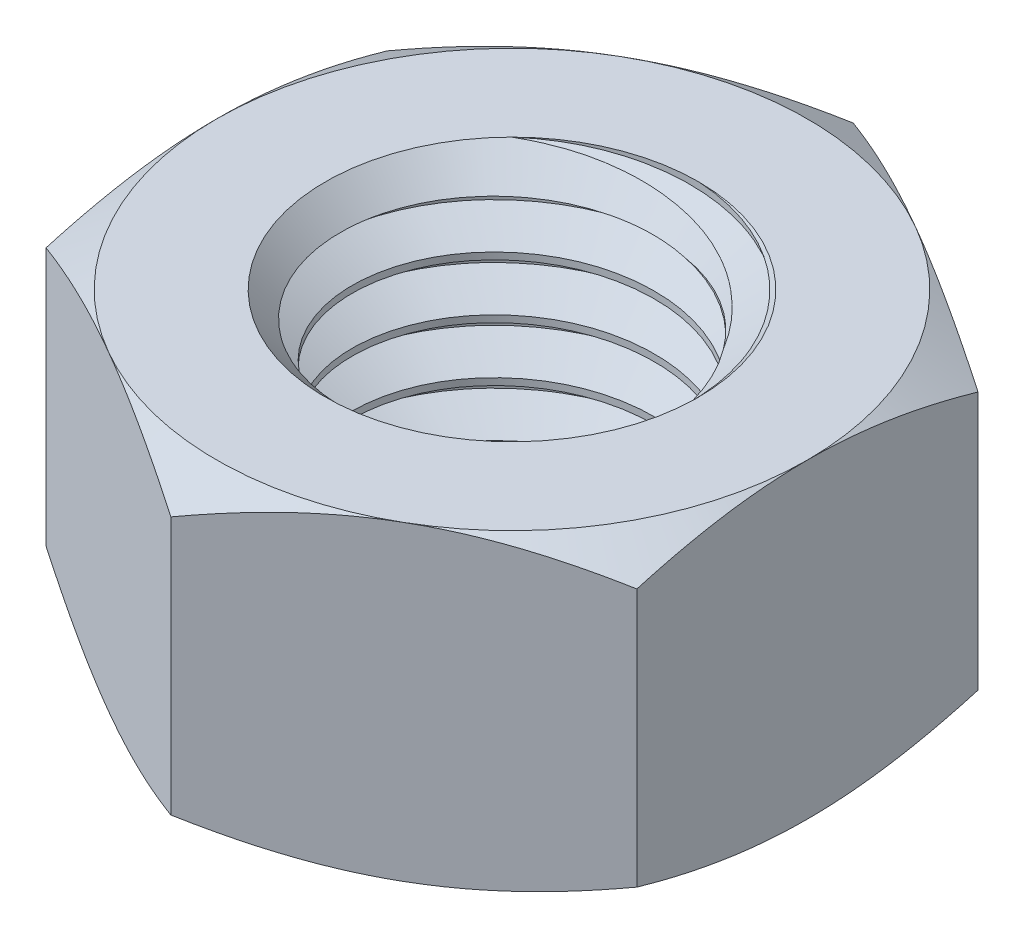
SolidWorks part; units mm, degrees
ref_plane "Front Plane" through (0, 0, 0) normal (0, 0, 1) x (1, 0, 0)
ref_plane "Top Plane" through (0, 0, 0) normal (0, 1, 0) x (1, 0, 0)
ref_plane "Right Plane" through (0, 0, 0) normal (1, 0, 0) x (0, 0, -1)
sketch "Sketch1" plane through (0, 0, 0) normal (0, 1, 0) x (1, 0, 0)
  line L0 (0, -6) -> (0, -4.25) construction
  line L1 (-9.5, 5.4848) -> (-9.5, -5.4848)
  line L2 (-9.5, -5.4848) -> (0, -10.9697)
  line L3 (0, -10.9697) -> (9.5, -5.4848)
  line L4 (9.5, -5.4848) -> (9.5, 5.4848)
  line L5 (9.5, 5.4848) -> (0, 10.9697)
  line L6 (0, 10.9697) -> (-9.5, 5.4848)
  line L7 (0, 6) -> (0, 4.25) construction
  circle A0 centre (0, 0) radius 9.5 construction
  circle A1 centre (0, 0) radius 6
  point P14 (0, 5.125)
  point P15 (0, 6)
  point P16 (0, 4.25)
  dimension "Pitch" = 1.75
  dimension "Thread Size" = 12
  dimension "Hex" = 19
extrude "Boss-Extrude1" add sketch "Sketch1" along normal mid plane 10
sketch "Sketch2" plane through (0, 5, 0) normal (0, 1, 0) x (1, 0, 0)
  circle A0 centre (0, 0) radius 6 construction
  circle A1 centre (0, 0) radius 6
sketch "Sketch5" plane through (0, 5, 0) normal (0, 1, 0) x (1, 0, 0)
  circle A0 centre (0, 0) radius 9.5 construction
  circle A1 centre (0, 0) radius 9.5
extrude "Cut-Extrude2" cut sketch "Sketch5" against normal through all draft 60 flip side to cut
mirror "Mirror1" about plane through (0, 0, 0) normal (0, 1, 0) of "Cut-Extrude2"
ref_axis "Center Axis 1" through (0, 5, 0) along (0, -1, 0)
ref_plane "Contact Plane 1" through (0, 5, 0) normal (0, 1, 0) x (-1, 0, 0)
ref_plane "Contact Plane 2" through (0, -5, 0) normal (0, -1, 0) x (1, 0, 0)
curve "Helix/Spiral1" pitch 1.75 height 11.75 radius 6 centre (0, 5, 0) axis (0, -1, 0) start towards (0, 0, 1) parameters "Pitch"=1.75
sketch "Sketch3" plane through (0, 0, 0) normal (1, 0, 0) x (0, 0, -1)
  line L0 (4.8633, 5.875) -> (6, 6.5312)
  line L1 (6, 6.5312) -> (6, 5)
  line L2 (6, 5) -> (4.8633, 5.6562)
  line L3 (4.8633, 5.6562) -> (4.8633, 5.875)
  line L4 (5.4317, 6.2031) -> (5.4317, 5.3281) construction
  line L5 (4.8633, 5.7656) -> (6, 5.7656) construction
  line L6 (6, 5) -> (-6, 5) construction
  dimension "D1" = 60
  dimension "D2" = 0.2188
  dimension "D3" = 0.875
sweep "Sweep1" add profiles "Sketch3" path "Helix/Spiral1"
sketch "Sketch9" plane through (0, 0, 0) normal (1, 0, 0) x (0, 0, -1)
  line L0 (9.5, 5) -> (-9.5, 5)
  line L1 (0, 5) -> (-8.2272, 5) construction
  line L2 (9.5, 10) -> (-9.5, 10)
  line L3 (-9.5, 10) -> (-9.5, 5)
  line L4 (9.5, 10) -> (9.5, 5)
  line L5 (10.9697, 0) -> (-10.9697, 0) construction
  line L6 (-10.9697, 4.1515) -> (-10.9697, -4.1515) construction
  line L7 (9.5, -10) -> (-9.5, -10)
  line L8 (-9.5, -10) -> (-9.5, -5)
  line L9 (9.5, -5) -> (-9.5, -5)
  line L10 (9.5, -10) -> (9.5, -5)
  point P3 (0, 5)
  point P14 (0, 0)
  dimension "D1" = 5
extrude "Cut-Extrude3" cut sketch "Sketch9" against normal through all both and the other way through all
sketch "Sketch10" plane through (0, 0, 0) normal (1, 0, 0) x (0, 0, -1)
  line L0 (6, 5) -> (4.8633, 5)
  line L3 (4.8633, 5.6562) -> (4.8633, 5.875) construction
  line L4 (0, -5) -> (0, 5) construction
  line L5 (-6, 0) -> (6, 0) construction
  line L6 (4.8633, 5) -> (4.8633, 3.8633)
  line L7 (4.8633, 3.8633) -> (6, 5)
  line L8 (4.8633, -5) -> (4.8633, -3.8633)
  line L9 (6, -5) -> (4.8633, -5)
  line L10 (4.8633, -3.8633) -> (6, -5)
  point P11 (0, 0)
  point P14 (0, 0)
revolve "Cut-Revolve1" cut sketch "Sketch10" angle 360 about L4
equation "\"D2@Sketch3\" = \"Pitch@Helix/Spiral1\"*.125"
equation "\"D3@Sketch3\" = \"Pitch@Helix/Spiral1\"*.5"
equation "\"D3@Helix/Spiral1\" = \"Height@Boss-Extrude1\"+\"Pitch@Helix/Spiral1\""
equation "\"Pitch@Helix/Spiral1\"=\"Pitch@Sketch1\""
equation "\"D1@Sketch9\"=\"Height@Boss-Extrude1\"/2"
